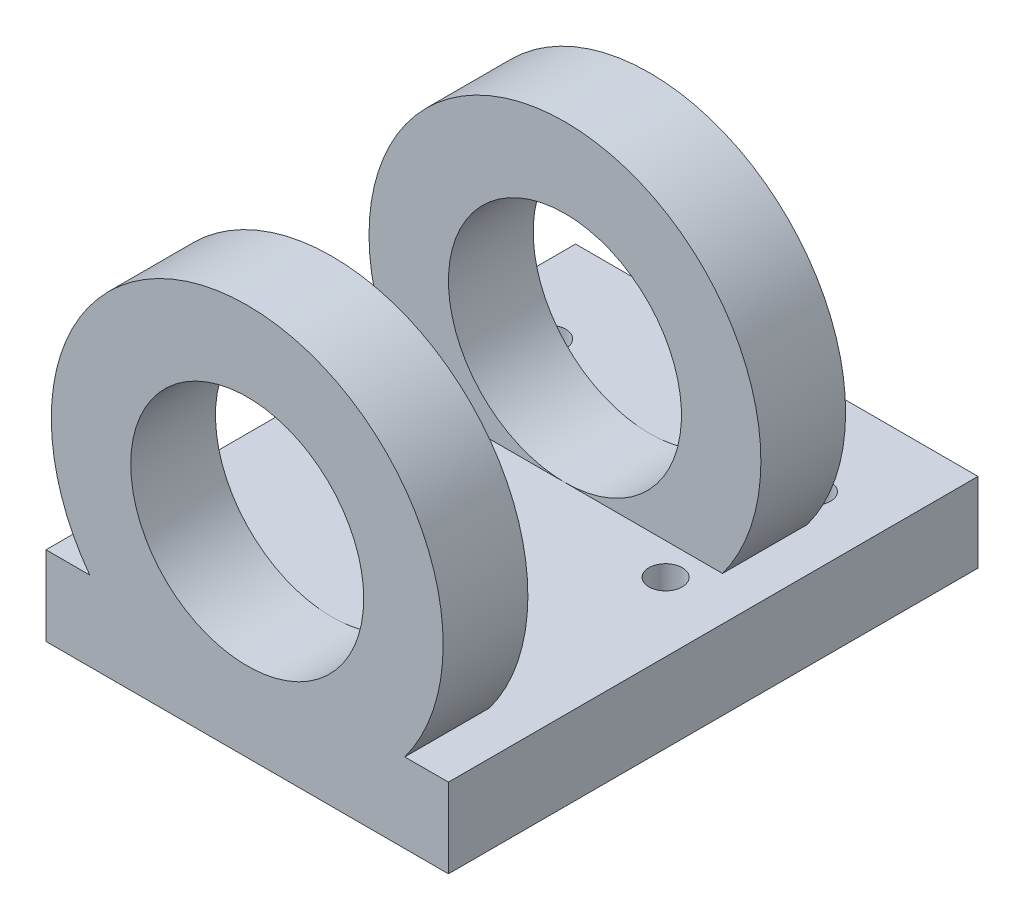
SolidWorks part; units mm, degrees
ref_plane "Plan de face" through (0, 0, 0) normal (0, 0, 1) x (1, 0, 0)
ref_plane "Plan de dessus" through (0, 0, 0) normal (0, 1, 0) x (1, 0, 0)
ref_plane "Plan de droite" through (0, 0, 0) normal (1, 0, 0) x (0, 0, -1)
sketch "Esquisse1" plane through (0, 0, 0) normal (0, 0, 1) x (1, 0, 0)
  line L0 (0, 0) -> (0, -18.5)
  line L1 (0, -18.5) -> (0, -11.0584)
  line L3 (-19, -18.5) -> (19, -18.5)
  line L4 (-19, -18.5) -> (-19, -11)
  line L5 (-19, -11) -> (19, -11)
  line L6 (19, -18.5) -> (19, -11)
  line L7 (-19, -18.5) -> (19, -11) construction
  line L8 (-19, -11) -> (19, -18.5) construction
  circle A0 centre (0, 0) radius 11
  circle A1 centre (0, 0) radius 18.5
  point P5 (0, -14.75)
  dimension "D1" = 22
  dimension "D2" = 37
  dimension "D3" = 38
extrude "Boss.-Extru.19" add sketch "Esquisse1" against normal blind 8 contours A1 | A0
extrude "Boss.-Extru.20" add sketch "Esquisse1<5>" along normal blind 30 and the other way blind 20 contours A1 L3 L6 L5 | A1 L5 L4 L3 | L5 A1 L0 | L0 A1 L5 region at (5.7672, -14.0591, 0) region at (-5.7672, -14.0591, 0) region at (14.0175, -15.5861, 0) region at (-14.0175, -15.5861, 0)
sketch "Esquisse1<5>" plane through (0, 0, 0) normal (0, 0, 1) x (1, 0, 0) same geometry as "Esquisse1"
pattern_linear "Répétition linéaire1" count 2 spacing 30 along (0, 0, 1) of "Boss.-Extru.19"
sketch "Esquisse8" plane through (0, -11, 0) normal (0, 1, 0) x (1, 0, 0)
  line L0 (-14.8745, 8) -> (14.8745, 0) construction
  line L1 (-14.8745, 0) -> (14.8745, 8) construction
  line L2 (-12.5, 11) -> (12.5, 11) construction
  line L3 (-12.5, 11) -> (-12.5, -3) construction
  line L4 (-12.5, -3) -> (12.5, -3) construction
  line L5 (12.5, 11) -> (12.5, -3) construction
  line L6 (-14.8745, 8) -> (-14.8745, 0)
  line L7 (0, 8) -> (-14.8745, 8)
  line L8 (14.8745, 8) -> (0, 8)
  line L9 (14.8745, 0) -> (14.8745, 8)
  line L10 (0, 0) -> (14.8745, 0)
  line L11 (-14.8745, 0) -> (0, 0)
  line L12 (-14.8745, 8) -> (-14.8745, 0)
  line L13 (0, 8) -> (-14.8745, 8)
  line L14 (14.8745, 8) -> (0, 8)
  line L15 (14.8745, 0) -> (14.8745, 8)
  line L16 (0, 0) -> (14.8745, 0)
  line L17 (-14.8745, 0) -> (0, 0)
  line L18 (-12.5, 11) -> (12.5, -3) construction
  line L19 (-12.5, -3) -> (12.5, 11) construction
  line L20 (0, 4) -> (-27.0621, 4) construction
  line L21 (0, 4) -> (0, -14.2427) construction
  circle A0 centre (-12.5, 11) radius 1.575
  circle A1 centre (12.5, 11) radius 1.575
  circle A2 centre (12.5, -3) radius 1.575
  circle A3 centre (-12.5, -3) radius 1.575
  point P2 (0, 4)
  point P11 (0, 4)
  point P15 (-14.8745, 0)
  dimension "D4" = 3.15
  dimension "D2" = 25
  dimension "D3" = 14
  dimension "D1" = 0
extrude "Enlèv. mat.-Extru.1" cut sketch "Esquisse8" against normal up to next contours A3 | A2 | A0 | A1
equation "\"D2@Esquisse1\"=\"D1@Esquisse1\"+15"
